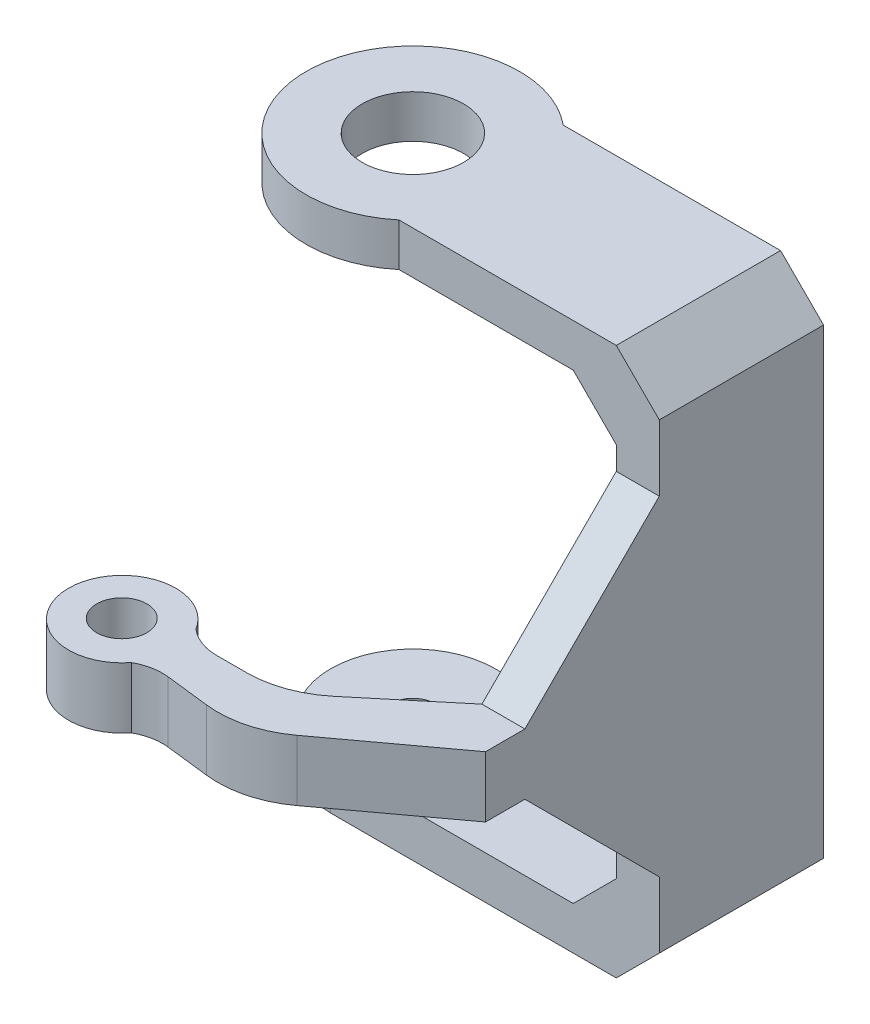
SolidWorks part; units mm, degrees
ref_plane "Front Plane" through (0, 0, 0) normal (0, 0, 1) x (1, 0, 0)
ref_plane "Top Plane" through (0, 0, 0) normal (0, 1, 0) x (1, 0, 0)
ref_plane "Right Plane" through (0, 0, 0) normal (1, 0, 0) x (0, 0, -1)
sketch "Sketch1" plane through (0, 0, 0) normal (0, 0, 1) x (1, 0, 0)
  line L0 (32.1661, 36.798) -> (35.1661, 39.798)
  line L1 (35.1661, 39.798) -> (38.1661, 36.798)
  line L2 (38.1661, 36.798) -> (38.1661, 4.578)
  line L3 (38.1661, 4.578) -> (35.1661, 1.578)
  line L4 (35.1661, 1.578) -> (32.1661, 4.578)
  line L5 (32.1661, 4.578) -> (35.1661, 7.578)
  line L6 (35.1661, 7.578) -> (35.1661, 33.798)
  line L7 (35.1661, 33.798) -> (32.1661, 36.798)
extrude "Boss-Extrude1" add sketch "Sketch1" along normal blind 5.73 and the other way blind 5.73
sketch "Sketch2" plane through (0, 0, 5.73) normal (0, 0, 1) x (1, 0, 0)
  line L0 (32.1661, 36.798) -> (20.0061, 36.798)
  line L2 (32.1661, 39.7973) -> (35.1655, 39.7973)
  line L3 (35.1661, 39.798) -> (32.1661, 36.798) construction
  line L4 (32.1661, 39.7973) -> (20.0061, 39.7973)
  line L5 (20.0061, 39.7973) -> (20.0061, 36.798)
  line L6 (35.1655, 39.7973) -> (32.1661, 36.798)
extrude "Boss-Extrude2" add sketch "Sketch2" against normal up to vertex (11.46 mm away) up to point (32.1661, 36.798, -5.73)
sketch "Sketch3" plane through (0, 0, 5.73) normal (0, 0, 1) x (1, 0, 0)
  line L0 (32.1661, 4.578) -> (35.1661, 1.578)
  line L1 (35.1661, 1.578) -> (32.1661, 1.578)
  line L3 (32.1661, 4.578) -> (20.0061, 4.578)
  line L4 (20.0061, 4.578) -> (20.0061, 1.578)
  line L5 (20.0061, 1.578) -> (32.1661, 1.578)
extrude "Boss-Extrude3" add sketch "Sketch3" against normal up to vertex (11.46 mm away) up to point (32.1661, 4.578, -5.73)
sketch "Sketch4" plane through (0, 39.7973, 0) normal (0, 1, 0) x (1, 0, 0)
  line L0 (20.0061, 5.73) -> (20.0061, -5.73)
  arc A0 (20.0061, 5.73) -> (20.0061, -5.73) centre (15.2449, 0) ccw
extrude "Boss-Extrude4" add sketch "Sketch4" against normal up to vertex (2.9993 mm away) up to point (20.0061, 36.798, 5.73)
sketch "Sketch7" plane through (0, 39.7973, 0) normal (0, 1, 0) x (1, 0, 0)
  circle A1 centre (15.2449, 0) radius 3.54
extrude "Cut-Extrude2" cut sketch "Sketch7" against normal up to vertex (2.9993 mm away) up to point (20.0061, 36.798, -5.73)
sketch "Sketch9" plane through (0, 1.578, 0) normal (0, -1, 0) x (-1, 0, 0)
  line L0 (-20.0061, -5.73) -> (-15.2449, -5.73)
  line L2 (-15.2449, 5.73) -> (-20.0061, 5.73)
  line L3 (-20.0061, 5.73) -> (-20.0061, -5.73)
  arc A0 (-15.2449, -5.73) -> (-15.2449, 5.73) centre (-15.2449, 0) ccw
extrude "Boss-Extrude5" add sketch "Sketch9" against normal blind 3 contours L0 A0 L2 L3
sketch "Sketch11" plane through (0, 1.578, 0) normal (0, -1, 0) x (-1, 0, 0)
  circle A1 centre (-15.2449, 0) radius 1.52
extrude "Cut-Extrude3" cut sketch "Sketch11" against normal blind 3
sketch "Sketch12" plane through (38.1661, 0, 0) normal (1, 0, 0) x (0, 0, -1)
  line L0 (-5.73, 32.188) -> (-5.73, 9.188)
  line L1 (-5.73, 4.578) -> (-5.73, 36.798) construction
  line L2 (-15.1062, 22.8118) -> (-15.1062, 18.5642)
  line L3 (-5.73, 32.188) -> (-15.1062, 22.8118)
  line L4 (-5.73, 9.188) -> (-15.1062, 18.5642)
extrude "Boss-Extrude6" add sketch "Sketch12" against normal up to vertex (3 mm away) up to point (35.1661, 33.798, 5.73)
ref_plane "Plane1" through (0, 18.5642, 0) normal (0, -1, 0) x (-1, 0, 0)
sketch "Sketch14" plane through (0, 18.5642, 0) normal (0, -1, 0) x (-1, 0, 0)
  line L0 (-38.1661, -15.1062) -> (-38.1661, -17.8562)
  line L1 (-38.1661, -17.8562) -> (-30.5948, -23.4403)
  line L2 (-35.1661, -15.1062) -> (-29.5336, -19.7941)
  line L3 (-25.6208, -24.7587) -> (-22.5655, -24.3987)
  line L4 (-35.1661, -15.1062) -> (-38.1661, -15.1062)
  line L5 (-25.0557, -21.4138) -> (-22.9776, -21.4138)
  arc A0 (-25.0557, -21.4138) -> (-29.5336, -19.7941) centre (-25.0557, -14.4138) cw
  arc A1 (-25.6208, -24.7587) -> (-30.5948, -23.4403) centre (-26.4399, -17.8068) cw
  arc A2 (-22.9776, -21.4138) -> (-20.6683, -20.5568) centre (-22.9776, -17.8738) ccw
  arc A3 (-22.5655, -24.3987) -> (-20.4234, -24.8248) centre (-22.1513, -27.9144) cw
  arc A4 (-20.4234, -24.8248) -> (-20.6683, -20.5568) centre (-17.4819, -22.515) ccw
extrude "Boss-Extrude7" add sketch "Sketch14" against normal blind 4.2475 contours A4 A2 L5 A0 L2 L4 L0 L1 A1 L3 A3
sketch "Sketch15" plane through (0, 18.5642, 0) normal (0, -1, 0) x (-1, 0, 0)
  circle A1 centre (-17.4176, -22.4821) radius 1.75
extrude "Cut-Extrude4" cut sketch "Sketch15" against normal blind 4.2475 contours A1
